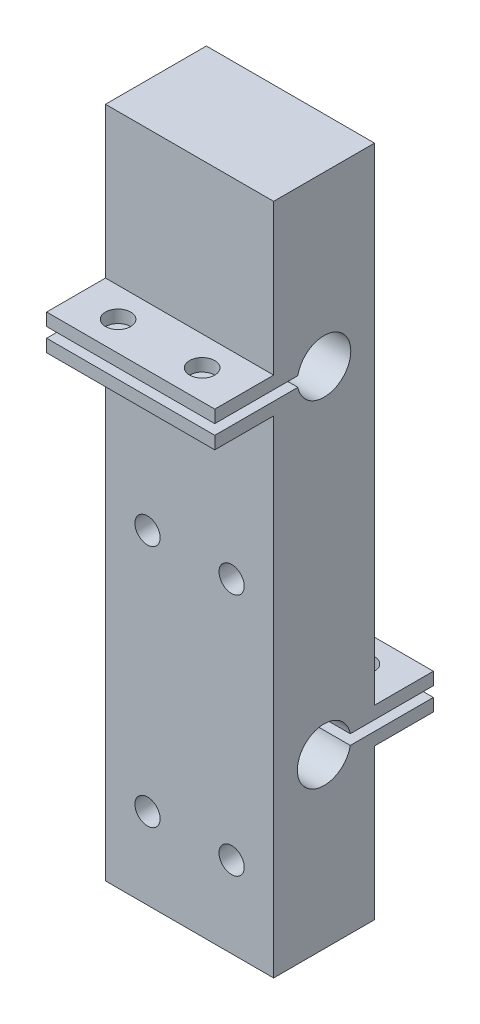
SolidWorks part; units mm, degrees
ref_plane "Front Plane" through (0, 0, 0) normal (0, 0, 1) x (1, 0, 0)
ref_plane "Top Plane" through (0, 0, 0) normal (0, 1, 0) x (1, 0, 0)
ref_plane "Right Plane" through (0, 0, 0) normal (1, 0, 0) x (0, 0, -1)
sketch "Sketch1" plane through (0, 0, 0) normal (0, 0, 1) x (1, 0, 0)
  line L1 (0, 0) -> (-20, 0)
  line L2 (0, 0) -> (0, 80)
  line L3 (0, 80) -> (-20, 80)
  line L4 (-20, 0) -> (-20, 80)
  dimension "D1" = 80
  dimension "D2" = 20
extrude "Boss-Extrude1" add sketch "Sketch1" along normal blind 12
sketch "Sketch3" plane through (0, 0, 0) normal (1, 0, 0) x (0, 0, -1)
  line L0 (-6, 80) -> (-6, 0) construction
  line L1 (-12, 80) -> (0, 80) construction
  line L2 (-12, 0) -> (0, 0) construction
  line L3 (-6, 0) -> (-12, 20) construction
  line L4 (-12, 0) -> (-12, 80) construction
  line L5 (-12, 20) -> (-6, 40) construction
  line L6 (-6, 40) -> (-12, 60) construction
  line L7 (-12, 60) -> (-6, 80) construction
  line L8 (-12, 60) -> (0, 60) construction
  line L9 (0, 0) -> (0, 80) construction
  line L10 (-12, 20) -> (0, 20) construction
  circle A0 centre (-6, 60) radius 3.175
  circle A1 centre (-6, 20) radius 3.175
  dimension "D1" = 6.35
extrude "Cut-Extrude1" cut sketch "Sketch3" against normal blind 12.7
sketch "Sketch6" plane through (0, 0, 0) normal (1, 0, 0) x (0, 0, -1)
  line L0 (-12, 62.1) -> (-12, 57.9)
  line L9 (-12, 57.9) -> (-19, 57.9)
  line L11 (-12, 62.1) -> (-19, 62.1)
  line L12 (-19, 57.9) -> (-19, 62.1)
  line L13 (-12, 60) -> (-19, 62.1) construction
  line L14 (-12, 60) -> (-19, 57.9) construction
  line L16 (7, 17.9) -> (0, 17.9)
  line L17 (7, 17.9) -> (7, 22.1)
  line L18 (7, 22.1) -> (0, 22.1)
  line L20 (7, 17.9) -> (0, 20) construction
  line L21 (7, 22.1) -> (0, 20) construction
  line L22 (0, 22.1) -> (0, 17.9)
  line L23 (0, 0) -> (0, 80) construction
  point P0 (-12, 60)
  point P2 (0, 20)
  dimension "D1" = 7
  dimension "D2" = 4.2
extrude "Boss-Extrude3" add sketch "Sketch6" against normal up to surface (20 mm away) up to face at (-20, 40, 6)
sketch "Sketch5" plane through (0, 0, 0) normal (1, 0, 0) x (0, 0, -1)
  line L0 (-12, 60) -> (0, 60) construction
  line L1 (-19, 59.4) -> (-9.1178, 59.4)
  line L3 (-19, 60.6) -> (-9.1178, 60.6)
  line L5 (-19, 62.1) -> (-19, 57.9) construction
  line L6 (-6, 20) -> (-2.825, 20) construction
  line L7 (-19, 60.6) -> (-19, 59.4)
  line L8 (7, 20.6) -> (7, 19.4)
  line L9 (7, 19.4) -> (-2.8822, 19.4)
  line L11 (7, 20.6) -> (-2.8822, 20.6)
  line L13 (-2.8822, 20.6) -> (-6, 20) construction
  line L14 (-6, 20) -> (-2.8822, 19.4) construction
  arc A0 (-9.1178, 59.4) -> (-9.1178, 60.6) centre (-6, 60) cw
  circle A1 centre (-6, 60) radius 3.175 construction
  arc A2 (-2.8822, 20.6) -> (-2.8822, 19.4) centre (-6, 20) cw
  circle A3 centre (-6, 20) radius 3.175 construction
  circle A4 centre (-6, 60) radius 3.175 construction
  circle A5 centre (-6, 60) radius 3.175 construction
  circle A6 centre (-6, 20) radius 3.175 construction
  point P0 (-12, 60)
  point P2 (0, 20)
  dimension "D2" = 1.2
extrude "Cut-Extrude2" cut sketch "Sketch5" against normal up to surface (20 mm away) up to face at (-20, 40, 6)
sketch "Sketch7" plane through (-20, 0, 0) normal (-1, 0, 0) x (0, 0, 1)
  line L0 (9.1178, 59.4) -> (9.2178, 59.4)
  line L1 (9.1178, 59.4) -> (19, 59.4) construction
  line L2 (9.2178, 59.4) -> (9.2178, 60.6)
  line L3 (19, 60.6) -> (9.1178, 60.6) construction
  line L4 (9.2178, 60.6) -> (9.1178, 60.6)
  line L5 (2.8822, 19.4) -> (2.7822, 19.4)
  line L6 (-7, 19.4) -> (2.8822, 19.4) construction
  line L7 (2.7822, 19.4) -> (2.7822, 20.6)
  line L8 (2.8822, 20.6) -> (-7, 20.6) construction
  line L9 (2.7822, 20.6) -> (2.8822, 20.6)
  arc A0 (9.1178, 59.4) -> (9.1178, 60.6) centre (6, 60) ccw construction
  arc A1 (9.1178, 59.4) -> (9.1178, 60.6) centre (6, 60) ccw
  arc A2 (2.8822, 20.6) -> (2.8822, 19.4) centre (6, 20) ccw construction
  arc A3 (2.8822, 20.6) -> (2.8822, 19.4) centre (6, 20) ccw
  dimension "D1" = 0.1
extrude "Boss-Extrude2" add sketch "Sketch7" against normal up to surface (7.3 mm away) up to face at (-12.7, 60, 6)
sketch "Sketch8" plane through (0, 62.1, 0) normal (0, 1, 0) x (1, 0, 0)
  line L0 (-20, -15.5) -> (0, -15.5) construction
  line L1 (-20, -19) -> (-20, -12) construction
  line L2 (0, -12) -> (0, -19) construction
  line L3 (-20, -15.5) -> (-15, -19) construction
  line L4 (-20, -19) -> (0, -19) construction
  line L5 (-15, -19) -> (-10, -15.5) construction
  line L6 (-10, -15.5) -> (-5, -19) construction
  line L7 (-5, -19) -> (0, -15.5) construction
  line L8 (-15, -19) -> (-15, -15.5) construction
  line L9 (-5, -19) -> (-5, -15.5) construction
  circle A0 centre (-15, -15.5) radius 1.5
  circle A1 centre (-5, -15.5) radius 1.5
  dimension "D1" = 3
extrude "Cut-Extrude3" cut sketch "Sketch8" against normal up to surface (4.2 mm away) up to face at (-10, 57.9, 15.5)
sketch "Sketch9" plane through (0, 22.1, 0) normal (0, 1, 0) x (1, 0, 0)
  line L0 (-20, 3.5) -> (0, 3.5) construction
  line L1 (-20, 0) -> (-20, 7) construction
  line L2 (0, 7) -> (0, 0) construction
  line L3 (-20, 3.5) -> (-15, 7) construction
  line L4 (-20, 7) -> (0, 7) construction
  line L5 (-15, 7) -> (-10, 3.5) construction
  line L6 (-10, 3.5) -> (-5, 7) construction
  line L7 (-5, 7) -> (0, 3.5) construction
  line L8 (-15, 7) -> (-15, 3.5) construction
  line L9 (-5, 7) -> (-5, 3.5) construction
  circle A0 centre (-15, 3.5) radius 1.5
  circle A1 centre (-5, 3.5) radius 1.5
  dimension "D1" = 3
extrude "Cut-Extrude4" cut sketch "Sketch9" against normal up to surface (4.2 mm away) up to face at (-10, 17.9, -3.5)
sketch "Sketch10" plane through (0, 0, 12) normal (0, 0, 1) x (1, 0, 0)
  line L0 (-20, 28.95) -> (0, 28.95) construction
  line L1 (-10, 0) -> (-20, 4.825) construction
  line L2 (-20, 4.825) -> (-10, 9.65) construction
  line L3 (-20, 57.9) -> (-20, 0) construction
  line L4 (0, 0) -> (0, 57.9) construction
  line L8 (-10, 28.95) -> (-10, 0) construction
  line L9 (-10, 9.65) -> (-20, 14.475) construction
  line L10 (-20, 0) -> (0, 0) construction
  line L11 (-20, 14.475) -> (-10, 19.3) construction
  line L12 (-10, 19.3) -> (-20, 24.125) construction
  line L13 (-20, 24.125) -> (-10, 28.95) construction
  line L14 (-20, 9.65) -> (0, 9.65) construction
  line L15 (-15, 9.65) -> (-10, 19.3) construction
  line L16 (-10, 19.3) -> (-5, 9.65) construction
  line L17 (-15, 9.65) -> (-20, 19.3) construction
  line L18 (-5, 9.65) -> (0, 19.3) construction
  line L19 (-20, 19.3) -> (0, 19.3) construction
  line L20 (-10, 28.95) -> (-10, 38.6) construction
  line L21 (-10, 38.6) -> (-20, 33.775) construction
  line L22 (-20, 33.775) -> (-10, 28.95) construction
  line L23 (-20, 38.6) -> (0, 38.6) construction
  line L24 (-20, 33.775) -> (0, 33.775) construction
  line L25 (-20, 24.125) -> (0, 24.125) construction
  circle A0 centre (-15, 9.65) radius 1.5
  circle A1 centre (-5, 9.65) radius 1.5
  circle A2 centre (-5, 38.6) radius 1.5
  circle A3 centre (-15, 38.6) radius 1.5
  dimension "D1" = 3
extrude "Cut-Extrude5" cut sketch "Sketch10" against normal up to surface (12 mm away) up to face at (-10, 51.05, 0)
sketch "Sketch11" plane through (0, 0, 0) normal (0, 0, -1) x (-1, 0, 0)
  circle A0 centre (5, 38.6) radius 2.75
  circle A1 centre (15, 38.6) radius 2.75
  circle A2 centre (5, 9.65) radius 2.75
  circle A3 centre (15, 9.65) radius 2.75
  dimension "D1" = 5.5
extrude "Cut-Extrude6" cut sketch "Sketch11" against normal blind 3.3
